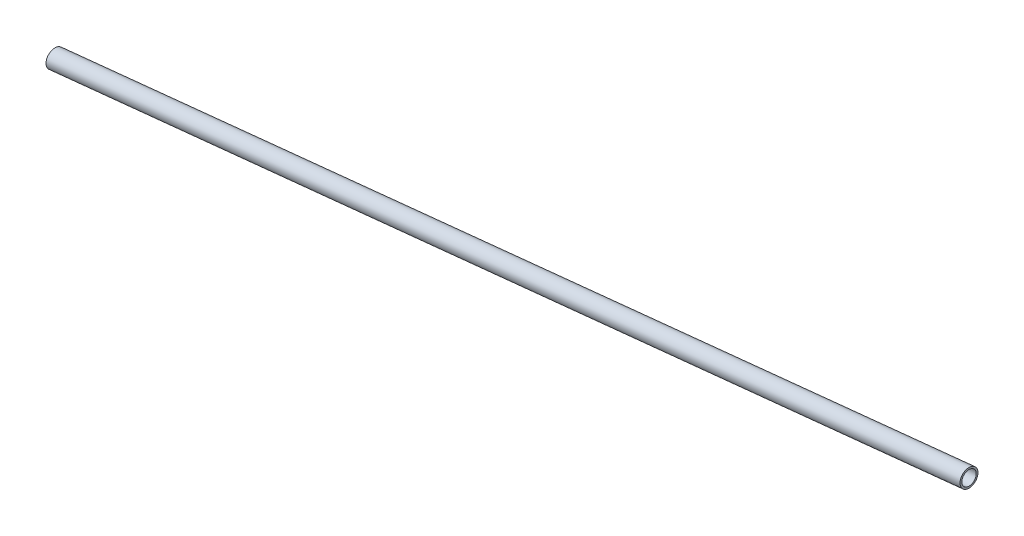
SolidWorks part; units mm, degrees
material "PVC Rigid"
ref_plane "Front Plane" through (0, 0, 0) normal (0, 0, 1) x (1, 0, 0)
ref_plane "Top Plane" through (0, 0, 0) normal (0, 1, 0) x (1, 0, 0)
ref_plane "Right Plane" through (0, 0, 0) normal (1, 0, 0) x (0, 0, -1)
sketch "Sketch1" plane through (0, 0, 0) normal (0, 0, 1) x (1, 0, 0)
  line L0 (0, 0) -> (900, -13.3527)
  line L1 (0, 0) -> (0, -522.6547)
  dimension "D1" = 89.15
  dimension "D2" = 900
sketch "Sketch3" plane through (0, 0, 0) normal (1, 0, 0) x (0, 0, -1)
  circle A0 centre (0, 0) radius 10
  dimension "D1" = 20
ref_plane "Plane1" through (900, 0, 0) normal (1, 0, 0) x (0, 0, -1)
sketch "Sketch5" plane through (0, 0, 0) normal (0, 1, 0) x (1, 0, 0)
  line L0 (0, 0) -> (900, 117.5286)
  line L1 (0, 0) -> (0, 457.9074)
  dimension "D1" = 82.56
  dimension "D2" = 900
sketch "Sketch7" plane through (900, 0, 0) normal (1, 0, 0) x (0, 0, -1)
  point P0 (0, -13.3527)
  point P2 (117.5286, 0)
sketch "Sketch8" plane through (900, 0, 0) normal (1, 0, 0) x (0, 0, -1)
  line L0 (0, -13.3527) -> (196.9901, -13.3527) construction
  line L1 (117.5286, 0) -> (117.5286, -13.3527) construction
  circle A0 centre (117.5286, -13.3527) radius 10
loft "Loft1" add profiles "Sketch3", "Sketch8" connector at (0, 0, -10) connector at (900, -13.3527, -127.5286)
sketch "Sketch9" plane through (900, 0, 0) normal (1, 0, 0) x (0, 0, -1)
  circle A0 centre (117.5286, -13.3527) radius 8
  circle A1 centre (117.5286, -13.3527) radius 10
  circle A2 centre (117.5286, -13.3527) radius 10
  dimension "D1" = 0
  dimension "D2" = 2
sketch "Sketch10" plane through (0, 0, 0) normal (-1, 0, 0) x (0, 0, 1)
  circle A0 centre (0, 0) radius 10 construction
  circle A1 centre (0, 0) radius 10
  circle A2 centre (0, 0) radius 8
  dimension "D1" = 2
loft "Cut-Loft1" cut section "Sketch10" section "Sketch9" connector at (0, 0.0468, -7.9999) connector at (900, -13.6612, -125.5226)
